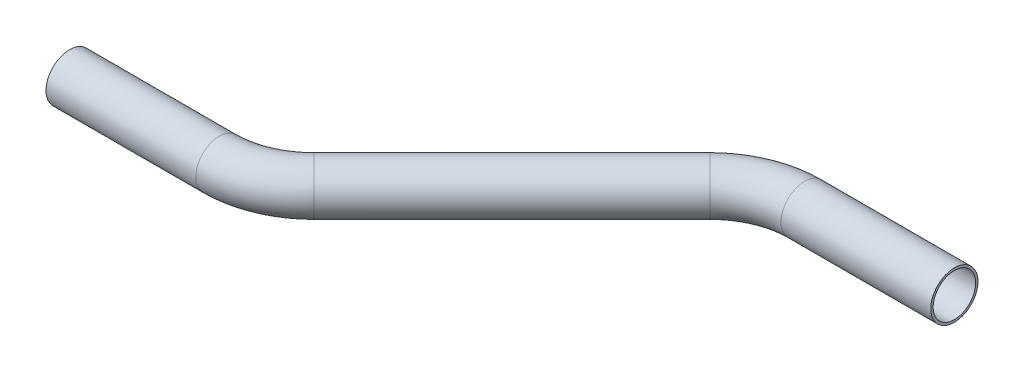
SolidWorks part; units mm, degrees
ref_plane "Front Plane" through (0, 0, 0) normal (0, 0, 1) x (1, 0, 0)
ref_plane "Top Plane" through (0, 0, 0) normal (0, 1, 0) x (1, 0, 0)
ref_plane "Right Plane" through (0, 0, 0) normal (1, 0, 0) x (0, 0, -1)
sketch "Sketch1" plane through (0, 0, 0) normal (0, 1, 0) x (1, 0, 0)
  line L0 (0, 0) -> (40.279, 0)
  line L1 (58.2395, 7.4395) -> (111.5167, 60.7167)
  line L2 (129.4772, 68.1561) -> (169.7561, 68.1561)
  arc A0 (111.5167, 60.7167) -> (129.4772, 68.1561) centre (129.4772, 42.7561) cw
  arc A1 (40.279, 0) -> (58.2395, 7.4395) centre (40.279, 25.4) ccw
  point P7 (118.9561, 68.1561)
  point P10 (50.8, 0)
  dimension "D5" = 25.4
  dimension "D1" = 50.8
  dimension "D2" = 50.8
  dimension "D3" = 135
  dimension "D4" = 68.1561
ref_plane "Plane1" through (0, 0, 0) normal (1, 0, 0) x (0, 0, -1)
sketch "Sketch2" plane through (0, 0, 0) normal (1, 0, 0) x (0, 0, -1)
  circle A0 centre (0, 0) radius 6.35
  circle A1 centre (0, 0) radius 5.715
  dimension "D1" = 12.7
  dimension "D2" = 0.635
sweep "Sweep1" add profiles "Sketch2" path "Sketch1"
